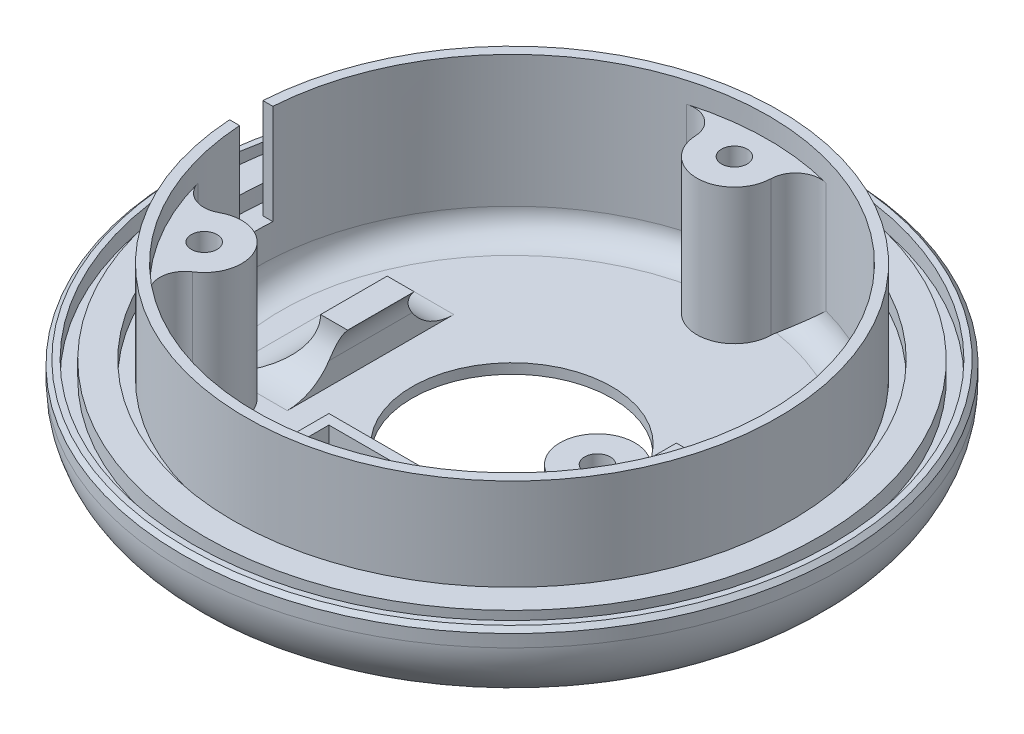
SolidWorks part; units mm, degrees
ref_plane "Plan de face" through (0, 0, 0) normal (0, 0, 1) x (1, 0, 0)
ref_plane "Plan de dessus" through (0, 0, 0) normal (0, 1, 0) x (1, 0, 0)
ref_plane "Plan de droite" through (0, 0, 0) normal (1, 0, 0) x (0, 0, -1)
sketch "Esquisse2" plane through (0, 0, 0) normal (0, 0, 1) x (1, 0, 0)
  line L0 (-39.6, 8) -> (-39.6, 10)
  line L1 (0, 0) -> (-32, 0)
  line L2 (-39.6, 10) -> (-38.4, 10)
  line L3 (-38.4, 10) -> (-38.4, 8)
  line L4 (0, 24.4124) -> (0, -18.1737) construction
  line L5 (0, 1.2) -> (-30.8, 1.2)
  line L7 (-32, 8) -> (-32, 20)
  line L8 (-32, 20) -> (-30.8, 20)
  line L9 (-30.8, 20) -> (-30.8, 1.2)
  line L10 (-32, 8) -> (-33.5, 8)
  line L11 (0, 0) -> (0, 1.2)
  line L12 (-38.4, 8) -> (-36.9, 8)
  line L13 (-36.9, 8) -> (-36.9, 10)
  line L17 (-36.9, 10) -> (-33.5, 10)
  line L18 (-33.5, 8) -> (-33.5, 10)
  arc A0 (-39.6, 8) -> (-32, 0) centre (-31.5895, 8) ccw
  circle A1 centre (-34.3, 4.5) radius 2.75
  dimension "D2" = 32
  dimension "D5" = 12
  dimension "D20" = 5.5
  dimension "D4" = 1.5
  dimension "D6" = 30.8
  dimension "D7" = 2
  dimension "D8" = 3.4
  dimension "D9" = 90
  dimension "D10" = 2
  dimension "D11" = 1.2
  dimension "D12" = 2
  dimension "D13" = 1.2
  dimension "D14" = 8
  dimension "D17" = 1.5
  dimension "D18" = 1.2
  dimension "D19" = 8
  dimension "D21" = 3.5
  dimension "D22" = 4.5
revolve "Révolution1" add sketch "Esquisse2" angle 360 about L4
sketch "Esquisse3" plane through (0, 0, 0) normal (1, 0, 0) x (0, 0, -1)
  line L0 (-39.6, 8) -> (39.6, 8) construction
  line L1 (2, 21.9768) -> (-2, 21.9768)
  line L2 (2, 21.9768) -> (2, 8)
  line L3 (2, 8) -> (-2, 8)
  line L4 (-2, 21.9768) -> (-2, 8)
  dimension "D1" = 2
  dimension "D2" = 4
extrude "Enlèv. mat.-Extru.1" cut sketch "Esquisse3" against normal blind 32
sketch "Esquisse4" plane through (0, 1.2, 0) normal (0, 1, 0) x (1, 0, 0)
  line L0 (4.2215, 26.9986) -> (4.2215, 30.6492)
  line L1 (-4.7785, 26.9986) -> (-4.7785, 30.5673)
  line L2 (21.2707, -17.1552) -> (24.4323, -18.9805)
  line L3 (25.7707, -9.361) -> (28.8614, -11.1454)
  line L4 (-25.4922, -9.8434) -> (-28.6538, -11.6687)
  line L5 (-20.9922, -17.6376) -> (-24.0828, -19.422)
  arc A0 (4.2215, 30.6492) -> (-4.7785, 30.5673) centre (0, 0) ccw
  circle A1 centre (-0.2785, 26.9986) radius 1.55
  arc A2 (24.4323, -18.9805) -> (28.8614, -11.1454) centre (0, 0) ccw
  arc A3 (-4.7785, 26.9986) -> (4.2215, 26.9986) centre (-0.2785, 26.9986) ccw
  circle A4 centre (23.5207, -13.2581) radius 1.55
  arc A5 (25.7707, -9.361) -> (21.2707, -17.1552) centre (23.5207, -13.2581) ccw
  arc A6 (-28.6538, -11.6687) -> (-24.0828, -19.422) centre (0, 0) ccw
  circle A7 centre (-23.2422, -13.7405) radius 1.55
  arc A8 (-20.9922, -17.6376) -> (-25.4922, -9.8434) centre (-23.2422, -13.7405) ccw
  circle A13 centre (23.5207, -13.2581) radius 1.55 [skipped]
  circle A14 centre (-23.2422, -13.7405) radius 1.55 [skipped]
  point P8 (0, 0)
  point P9 (0, 0)
  point P10 (0, 0)
  point P11 (0, 0)
  point P12 (0, 0)
  point P13 (0, 0)
  point P16 (0, 0)
  point P21 (0, 0)
  point P33 (0, 0)
  point P34 (0, 0)
  point P35 (0, 0)
  point P37 (0, 0)
  point P41 (0, 0)
  dimension "D1" = 3.1
  dimension "D3" = 3
  dimension "D4" = 3
  dimension "D5" = 4.5
  dimension "D2" = 27
extrude "Boss.-Extru.1" add sketch "Esquisse4" along normal blind 16.3
fillet "Congé1" radius 3 9 edges at (0.2815, 1.2, 30.7987) (26.5317, 1.2, -15.6432) (-26.8132, 1.2, -15.1555) (-28.5326, 9.35, 11.5988) (28.7399, 9.35, 11.0752) (24.3111, 9.35, 18.9106) (-4.7785, 9.35, -30.4271) (4.2215, 9.35, -30.5093) (-23.9613, 9.35, 19.3518)
chamfer "Chanfrein1" distance 0.5 angle 45 1 edges at (0, 10, 39.6)
sketch "Esquisse5" plane through (0, 1.2, 0) normal (0, 1, 0) x (1, 0, 0)
  circle A0 centre (0, 0) radius 12
  circle A1 centre (0, -20) radius 2.5
  dimension "D1" = 24
  dimension "D2" = 5
  dimension "D3" = 20
extrude "Enlèv. mat.-Extru.2" cut sketch "Esquisse5" against normal blind 10
sketch "Esquisse6" plane through (0, 1.2, 0) normal (0, 1, 0) x (1, 0, 0)
  line L1 (-17, 4) -> (-19, 4)
  line L2 (-17, 4) -> (-17, -4)
  line L3 (-17, -4) -> (-19, -4)
  line L4 (-19, 4) -> (-19, -4)
  line L5 (17, 4) -> (19, 4)
  line L6 (17, 4) -> (17, -4)
  line L7 (17, -4) -> (19, -4)
  line L8 (19, 4) -> (19, -4)
  line L9 (12, -15) -> (-7, -15)
  line L10 (12, -15) -> (12, -25)
  line L11 (12, -25) -> (-7, -25)
  line L12 (-7, -15) -> (-7, -25)
  line L13 (-8.2, -13.8) -> (13.2, -13.8)
  line L14 (-8.2, -13.8) -> (-8.2, -26.2)
  line L15 (-8.2, -26.2) -> (13.2, -26.2)
  line L16 (13.2, -13.8) -> (13.2, -26.2)
  circle A0 centre (0, -20) radius 2.5 construction
  dimension "D1" = 2
  dimension "D2" = 2
  dimension "D3" = 17
  dimension "D4" = 17
  dimension "D5" = 4
  dimension "D6" = 8
  dimension "D7" = 4
  dimension "D8" = 8
  dimension "D9" = 10
  dimension "D10" = 19
  dimension "D11" = 7
  dimension "D12" = 5
  dimension "D13" = 1.2
  dimension "D14" = 1.2
  dimension "D15" = 1.2
  dimension "D16" = 1.2
extrude "Boss.-Extru.2" add sketch "Esquisse6" along normal blind 6
sketch "Esquisse7" plane through (0, 0, 4) normal (0, 0, 1) x (1, 0, 0)
  line L0 (-17, 7.2) -> (-15.75, 7.2)
  line L1 (-17, 5.7) -> (-15.75, 7.2)
  line L2 (-17, 7.2) -> (-17, 1.2) construction
  line L3 (-17, 5.7) -> (-17, 7.2)
  line L4 (17, 7.2) -> (17, 5.7)
  line L5 (17, 7.2) -> (17, 1.2) construction
  line L6 (17, 5.7) -> (15.75, 7.2)
  line L7 (15.75, 7.2) -> (17, 7.2)
  line L8 (17, 7.2) -> (19, 7.2) construction
  dimension "D1" = 1.5
  dimension "D2" = 1.5
  dimension "D3" = 1.25
  dimension "D4" = 1.25
extrude "Boss.-Extru.3" add sketch "Esquisse7" against normal blind 8
fillet "Congé2" radius 5 2 edges at (17, 5.7, 0) (-17, 5.7, 0)
fillet "Congé3" radius 1 1 edges at (0, 0, 17.5)
fillet "Congé4" radius 6 6 edges at (18, 1.2, 4) (-19, 1.2, 0) (-18, 1.2, 4) (-18, 1.2, -4) (19, 1.2, 0) (18, 1.2, -4)
